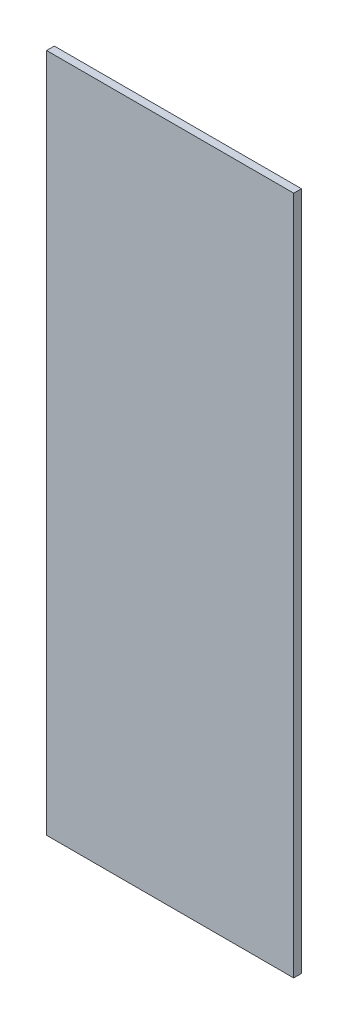
SolidWorks part; units mm, degrees
ref_plane "Front Plane" through (0, 0, 0) normal (0, 0, 1) x (1, 0, 0)
ref_plane "Top Plane" through (0, 0, 0) normal (0, 1, 0) x (1, 0, 0)
ref_plane "Right Plane" through (0, 0, 0) normal (1, 0, 0) x (0, 0, -1)
sketch "Sketch1" plane through (0, 0, 0) normal (0, 0, 1) x (1, 0, 0)
  line L1 (0, 0) -> (50.8, 0)
  line L2 (0, 0) -> (0, 139.7)
  line L3 (0, 139.7) -> (50.8, 139.7)
  line L4 (50.8, 0) -> (50.8, 139.7)
  dimension "D1" = 139.7
  dimension "D2" = 50.8
extrude "Boss-Extrude1" add sketch "Sketch1" along normal blind 1.5875
